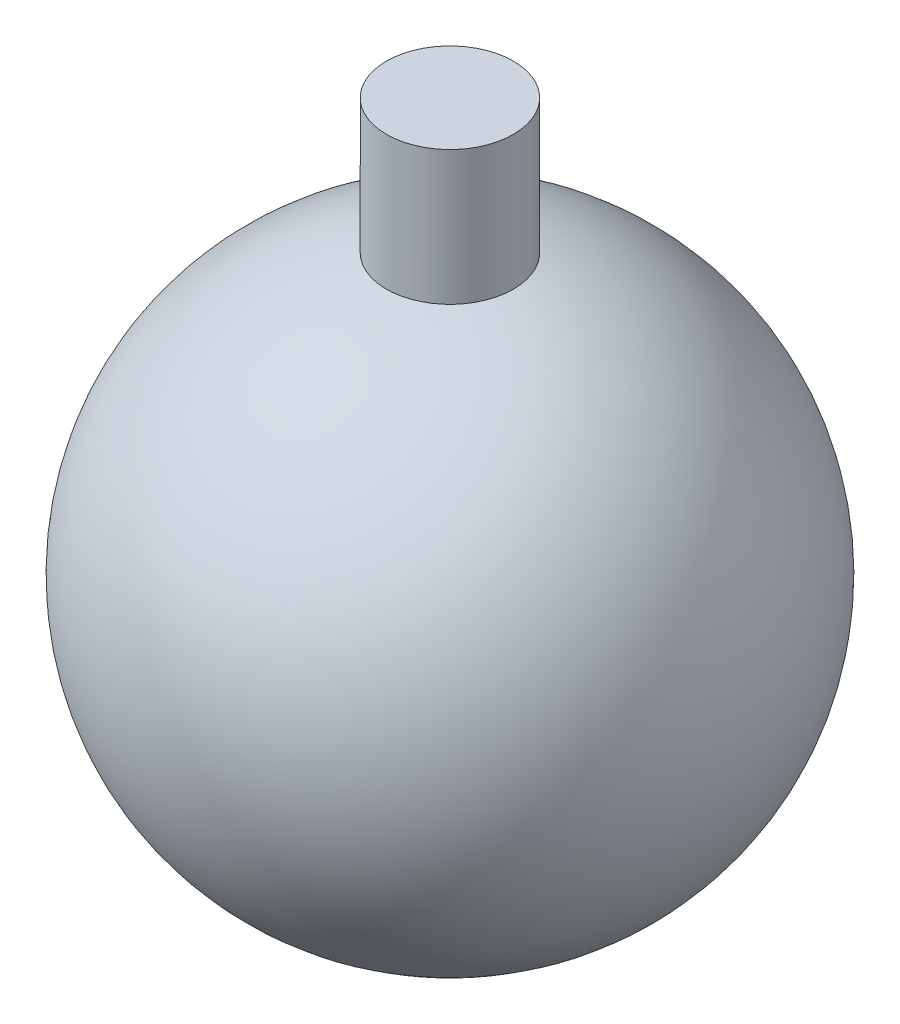
SolidWorks part; units mm, degrees
ref_plane "Front Plane" through (0, 0, 0) normal (0, 0, 1) x (1, 0, 0)
ref_plane "Top Plane" through (0, 0, 0) normal (0, 1, 0) x (1, 0, 0)
ref_plane "Right Plane" through (0, 0, 0) normal (1, 0, 0) x (0, 0, -1)
sketch "Sketch1" plane through (0, 0, 0) normal (0, 0, 1) x (1, 0, 0)
  line L0 (0, 9) -> (0, -9)
  arc A0 (0, 9) -> (0, -9) centre (0, 0) ccw
  dimension "D1" = 18
ref_axis "Axis1" through (0, 9.9, 0) along (0, -1, 0)
revolve "Revolve3" add sketch "Sketch1" angle 360 about L0
sketch "Sketch3" plane through (0, 0, 0) normal (0, 1, 0) x (1, 0, 0)
  circle A0 centre (0, 0) radius 2
extrude "Boss-Extrude1" add sketch "Sketch3" along normal blind 13
